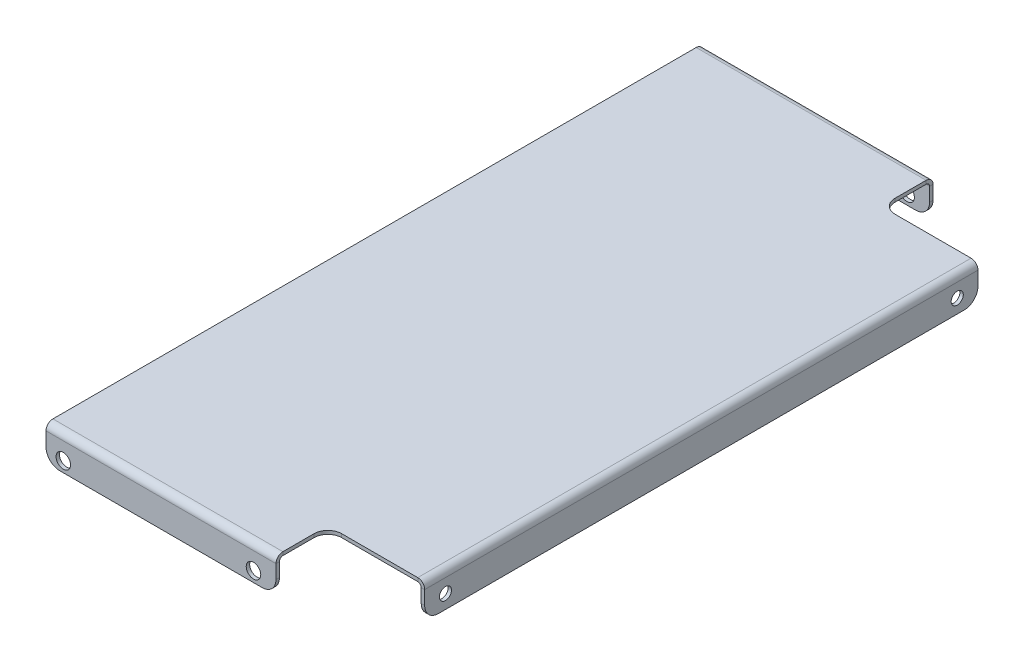
SolidWorks part; units mm, degrees
note: The reader was unsure of these and kept them because the rebuilt part matched: flange length of "Ребро-кромка1", "Ребро-кромка2".
material "Ст 3 ГОСТ 380-88"
ref_plane "Спереди" through (0, 0, 0) normal (0, 0, 1) x (1, 0, 0)
ref_plane "Сверху" through (0, 0, 0) normal (0, 1, 0) x (1, 0, 0)
ref_plane "Справа" through (0, 0, 0) normal (1, 0, 0) x (0, 0, -1)
other "Configuration Table"
sketch "Эскиз1" plane through (0, 0, 0) normal (0, 1, 0) x (1, 0, 0)
  line L1 (0, 0) -> (66.5, 0)
  line L2 (0, 0) -> (0, -188)
  line L3 (0, -188) -> (66.5, -188)
  line L4 (94.5, -14) -> (94.5, -174)
  line L7 (94.5, -14) -> (66.5, -14)
  line L8 (66.5, 0) -> (66.5, -14)
  line L11 (94.5, -174) -> (66.5, -174)
  line L12 (66.5, -188) -> (66.5, -174)
  dimension "D1" = 94.5
  dimension "D2" = 188
  dimension "D3" = 28
  dimension "D4" = 14
  dimension "D5" = 14
  dimension "D6" = 28
base flange "Базовая кромка1" sketch "Эскиз1" thickness 1 reverse thickness direction no parameters "D1"=4
edge flange "Ребро-кромка1" sketch "Эскиз8" flange angle 90 flange length 10 flange position material inside bend radius 1 thickness 1 relief rectangular parameters "D6"=10
sketch "Эскиз8" plane through (94.5, -1, 0) normal (-1, 0, 0) x (0, 0, -1)
  line L2 (-174, 0) -> (-174, 9)
  line L3 (-174, 9) -> (-14, 9)
  line L4 (-14, 9) -> (-14, 0)
  line L5 (-14, 0) -> (-174, 0) construction
  line L6 (-14, 0) -> (-174, 0)
bend "EdgeBend1" bend radius 1 bend angle 90 parameters "D5"=1
edge flange "Ребро-кромка2" sketch "Эскиз13" flange profiles "Эскиз13", "Эскиз14" flange angle 90 flange length 10 flange position material outside bend radius 1 thickness 1 relief rectangular parameters "D6"=10, "D8"=1
sketch "Эскиз13" plane through (0, -1, 188) normal (0, 0, -1) x (1, 0, 0)
  line L2 (0, 0) -> (0, 9)
  line L3 (0, 9) -> (66.5, 9)
  line L4 (66.5, 9) -> (66.5, 0)
  line L5 (66.5, 0) -> (0, 0) construction
  line L6 (66.5, 0) -> (0, 0)
sketch "Эскиз14" plane through (0, -1, 0) normal (0, 0, 1) x (-1, 0, 0)
  line L0 (0, 0) -> (-66.5, 0) construction
  line L1 (0, 0) -> (-66.5, 0)
  line L2 (0, 0) -> (0, 9)
  line L3 (0, 9) -> (-66.5, 9)
  line L4 (-66.5, 9) -> (-66.5, 0)
bend "EdgeBend2" bend radius 1 bend angle 90 parameters "D5"=2
bend "EdgeBend3" bend radius 1 bend angle 90 parameters "D5"=3
sketch "Эскиз15" plane through (94.5, 0, 0) normal (1, 0, 0) x (0, 0, -1)
  line L0 (-14, -1) -> (-1, -1) construction
  line L1 (0, -10) -> (0, -2) construction
  line L2 (-188, -2) -> (-188, -10) construction
  circle A0 centre (-168, -6) radius 1.75
  circle A1 centre (-20, -6) radius 1.75
  point P8 (0, 0)
  dimension "D4" = 3.5
  dimension "D5" = 3.5
  dimension "D1" = 5
  dimension "D2" = 20
  dimension "D3" = 20
extrude "Вырез-Вытянуть1" cut sketch "Эскиз15" against normal blind 10 normal cut yes
fillet "Скругление1" radius 4 8 edges at (66.5, -0.5, 14) (66.5, -0.5, 174) (66.5, -10, 188.5) (0, -10, 188.5) (0, -10, -0.5) (66.5, -10, -0.5) (94, -10, 14) (94, -10, 174)
sketch "Эскиз16" plane through (0, 0, 189) normal (0, 0, 1) x (1, 0, 0)
  line L0 (66.5, -1) -> (70.5, -1) construction
  line L1 (0, -6) -> (0, -2) construction
  line L2 (0, 0) -> (0, -2) construction
  circle A0 centre (5, -7) radius 2.1
  circle A1 centre (60, -7) radius 2.1
  point P8 (0, 0)
  point P11 (-3.4416, 19.8717)
  point P12 (0, 0)
  point P13 (64.2641, -7.1022)
  dimension "D2" = 4.2
  dimension "D1" = 6
  dimension "D3" = 60
  dimension "D4" = 5
extrude "Вырез-Вытянуть2" cut sketch "Эскиз16" against normal through all normal cut yes
sketch "Сгиб-Линии1" [suppressed] plane through (0, 0, 0) normal (0, 1, 0) x (1, 0, 0)
sketch "Граничная рамка1" [suppressed] plane through (0, 0, 0) normal (0, 1, 0) x (1, 0, 0)
sheet metal parameters "Листовой металл3" thickness 1 parameters "D1"=4
flat pattern "Развертка3" [suppressed]
sketch "Сгиб-Линии2" plane through (0, 0, 0) normal (0, 1, 0) x (1, 0, 0)
sketch "Граничная рамка2" [suppressed] plane through (0, 0, 0) normal (0, 1, 0) x (1, 0, 0)
sheet metal parameters "Листовой металл4" thickness 1 parameters "D1"=4
flat pattern "Развертка3" [suppressed]
sketch "Сгиб-Линии2" plane through (0, 0, 0) normal (0, 1, 0) x (1, 0, 0)
sketch "Граничная рамка2" [suppressed] plane through (0, 0, 0) normal (0, 1, 0) x (1, 0, 0)
bend of the flat pattern "Плоское состояние-<EdgeBend1>1"
sheet metal parameters "Листовой металл5" thickness 1 parameters "D1"=4
flat pattern "Развертка3" [suppressed]
sketch "Сгиб-Линии2" plane through (0, 0, 0) normal (0, 1, 0) x (1, 0, 0)
sketch "Граничная рамка2" [suppressed] plane through (0, 0, 0) normal (0, 1, 0) x (1, 0, 0)
bend of the flat pattern "Плоское состояние-<EdgeBend1>1"
bend of the flat pattern "Плоское состояние-<EdgeBend2>1"
bend of the flat pattern "Плоское состояние-<EdgeBend3>1"
sheet metal parameters "Листовой металл6" thickness 1 parameters "D1"=4
flat pattern "Развертка3" [suppressed]
sketch "Сгиб-Линии2" plane through (0, 0, 0) normal (0, 1, 0) x (1, 0, 0)
sketch "Граничная рамка2" [suppressed] plane through (0, 0, 0) normal (0, 1, 0) x (1, 0, 0)
bend of the flat pattern "Плоское состояние-<EdgeBend1>1"
bend of the flat pattern "Плоское состояние-<EdgeBend2>1"
bend of the flat pattern "Плоское состояние-<EdgeBend3>1"
sheet metal parameters "Листовой металл7" thickness 1 parameters "D1"=4
flat pattern "Развертка3"
sketch "Сгиб-Линии2" plane through (0, 0, 0) normal (0, 1, 0) x (1, 0, 0)
  line L0 (66.5, 0.1781) -> (0, 0.1781) construction
  line L1 (0, -188.1781) -> (66.5, -188.1781) construction
  line L2 (93.6781, -174) -> (93.6781, -14) construction
  line L3 (66.5, 0.1781) -> (0, 0.1781) construction
  line L4 (0, -188.1781) -> (66.5, -188.1781) construction
  line L5 (93.6781, -174) -> (93.6781, -14) construction
sketch3d "Граничная рамка2" [suppressed]
  line L0 (102.8563, 9.3561, 0) -> (102.8562, -197.3562, 0) construction
  line L1 (0.0001, 9.3562, 0) -> (0, -197.3562, 0) construction
  line L2 (102.8563, 9.3561, 0) -> (0.0001, 9.3562, 0) construction
  line L3 (102.8562, -197.3562, 0) -> (0, -197.3562, 0) construction
bend of the flat pattern "Плоское состояние-<EdgeBend1>1"
bend of the flat pattern "Плоское состояние-<EdgeBend2>1"
bend of the flat pattern "Плоское состояние-<EdgeBend3>1"
